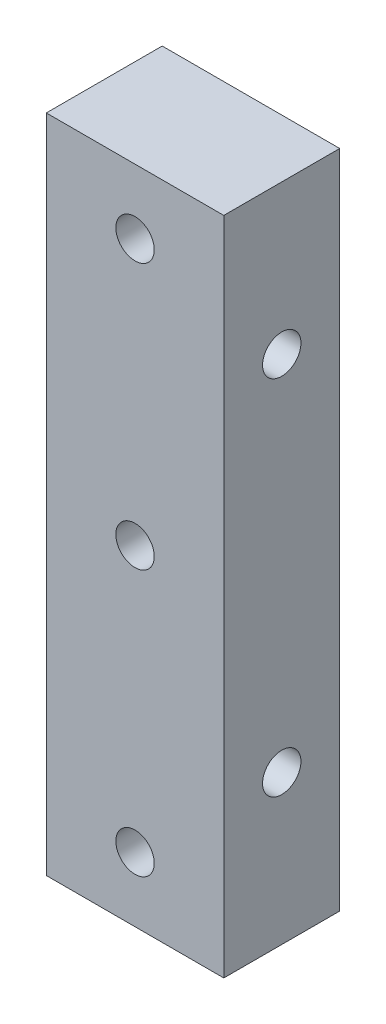
SolidWorks part; units mm, degrees
material "6061-T6 (SS)"
ref_plane "Front Plane" through (0, 0, 0) normal (0, 0, 1) x (1, 0, 0)
ref_plane "Top Plane" through (0, 0, 0) normal (0, 1, 0) x (1, 0, 0)
ref_plane "Right Plane" through (0, 0, 0) normal (1, 0, 0) x (0, 0, -1)
sketch "Sketch1" plane through (0, 0, 0) normal (0, 0, 1) x (1, 0, 0)
  line L1 (-9.3345, 34.7345) -> (9.3345, 34.7345)
  line L2 (-9.3345, 34.7345) -> (-9.3345, -34.7345)
  line L3 (-9.3345, -34.7345) -> (9.3345, -34.7345)
  line L4 (9.3345, 34.7345) -> (9.3345, -34.7345)
  line L5 (-9.3345, 34.7345) -> (9.3345, -34.7345) construction
  line L6 (-9.3345, -34.7345) -> (9.3345, 34.7345) construction
  point P0 (0, 0)
  dimension "D1" = 18.669
  dimension "D2" = 69.469
extrude "Boss-Extrude1" add sketch "Sketch1" along normal blind 12.192
sketch "Sketch2" plane through (9.3345, 0, 0) normal (1, 0, 0) x (0, 0, -1)
  line L0 (-6.096, 19.05) -> (-6.096, -19.05) construction
  line L2 (0, -34.7345) -> (0, 34.7345) construction
  line L3 (-12.192, 34.7345) -> (0, 34.7345) construction
  point P2 (-6.096, 0)
  point P3 (-6.096, 34.7345)
  point P7 (0, 0)
  dimension "D2" = 38.1
hole_wizard "Tap Drill for #10-32 Tap1" positions "Sketch3" profile "Sketch4" hole size "#10-32" standard "ANSI Inch" end condition through all
sketch "Sketch3" plane through (9.3345, 0, 0) normal (1, 0, 0) x (0, 0, -1)
  point P0 (-6.096, 19.05)
  point P3 (-6.096, -19.05)
sketch "Sketch4" plane through (9.3345, 19.05, 6.096) normal (0, 1, 0) x (0, 0, -1)
  line L0 (0, 0) -> (0, 18.669)
  line L1 (0, 18.669) -> (2.0193, 18.669)
  line L2 (2.0193, 18.669) -> (2.0193, 0)
  line L5 (2.0193, 0) -> (0, 0)
  line L11 (0, -6.35) -> (0, 107.95) construction
  dimension "Thru Hole Dia." = 4.0386
  dimension "Thru Hole Depth" = 18.669
sketch "Sketch5" plane through (0, 0, 12.192) normal (0, 0, 1) x (1, 0, 0)
  line L0 (0, 27.94) -> (0, -27.94) construction
  point P3 (0, 0)
  dimension "D1" = 55.88
hole_wizard "Tap Drill for #10-32 Tap2" positions "Sketch6" profile "Sketch8" hole size "#10-32" standard "ANSI Inch" end condition through all
sketch "Sketch6" plane through (0, 0, 12.192) normal (0, 0, 1) x (1, 0, 0)
  point P0 (0, 27.94)
  point P3 (0, -27.94)
  point P7 (0, 0)
sketch "Sketch8" plane through (0, 27.94, 12.192) normal (1, 0, 0) x (0, -1, 0)
  line L0 (0, 0) -> (0, 12.192)
  line L1 (0, 12.192) -> (2.0193, 12.192)
  line L2 (2.0193, 12.192) -> (2.0193, 0)
  line L5 (2.0193, 0) -> (0, 0)
  line L11 (0, -6.35) -> (0, 107.95) construction
  dimension "Thru Hole Dia." = 4.0386
  dimension "Thru Hole Depth" = 12.192
sketch "Sketch9" plane through (0, -34.7345, 0) normal (0, -1, 0) x (1, 0, 0)
  line L0 (-9.3345, 12.192) -> (9.3345, 12.192) construction
  line L1 (-9.3345, 0) -> (9.3345, 0) construction
  point P0 (0, -6.858)
  point P4 (0, 0)
  dimension "D1" = 19.05
